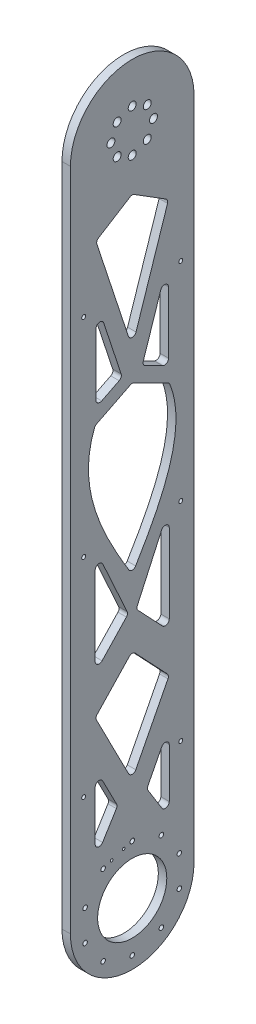
SolidWorks part; units mm, degrees
material "1060 Alloy"
ref_plane "Front Plane" through (0, 0, 0) normal (0, 0, 1) x (1, 0, 0)
ref_plane "Top Plane" through (0, 0, 0) normal (0, 1, 0) x (1, 0, 0)
ref_plane "Right Plane" through (0, 0, 0) normal (1, 0, 0) x (0, 0, -1)
sketch "Sketch1" plane through (0, 0, 0) normal (1, 0, 0) x (0, -1, 0)
  line L0 (0, 0) -> (500, 0) construction
  line L1 (0, 46.5) -> (500, 46.5)
  line L2 (0, -46.5) -> (500, -46.5)
  arc A0 (0, 46.5) -> (0, -46.5) centre (0, 0) ccw
  arc A1 (500, -46.5) -> (500, 46.5) centre (500, 0) ccw
  circle A2 centre (0, 0) radius 16 construction
  circle A3 centre (-16, 0) radius 3
  circle A4 centre (-11.3137, 11.3137) radius 3
  circle A5 centre (0, 16) radius 3
  circle A6 centre (11.3137, 11.3137) radius 3
  circle A7 centre (16, 0) radius 3
  circle A8 centre (11.3137, -11.3137) radius 3
  circle A27 centre (500, 0) radius 37.25 construction
  circle A28 centre (537.25, 0) radius 1.7
  circle A29 centre (500, 0) radius 37.25 construction
  circle A30 centre (537.25, 0) radius 1.7
  circle A31 centre (530.1359, -21.895) radius 1.7
  circle A32 centre (511.5109, -35.4269) radius 1.7
  circle A33 centre (488.4891, -35.4269) radius 1.7
  circle A34 centre (469.8641, -21.895) radius 1.7
  circle A35 centre (462.75, 0) radius 1.7
  circle A36 centre (469.8641, 21.895) radius 1.7
  circle A37 centre (488.4891, 35.4269) radius 1.7
  circle A38 centre (511.5109, 35.4269) radius 1.7
  circle A39 centre (530.1359, 21.895) radius 1.7
  circle A40 centre (500, 0) radius 26
  circle A41 centre (0, -16) radius 3
  circle A42 centre (-11.3137, -11.3137) radius 3
  point P3 (250, 0)
  point P25 (0, 0)
  point P52 (500, 0)
  point P61 (500, 0)
  dimension "D3" = 32
  dimension "D4" = 6
  dimension "D2" = 74.5
  dimension "D7" = 3.4
  dimension "D8" = 3.4
  dimension "D10" = 52
  dimension "D6" = 46.5
  dimension "D1" = 500
  dimension "D5" = 8
  dimension "D9" = 10
extrude "Boss-Extrude1" add sketch "Sketch1" along normal blind 6.35 contours L2 A1 L1 A0 A40 A39 A38 A37 A36 A35 A34 A33 A32 A31 A28 A8 A7 A6 A5 A4 A3 region at (0, -240.225, 0)
ref_axis "Axis1" through (6.35, -500, 0) along (-1, 0, 0)
sketch "Sketch3" plane through (6.35, 0, 0) normal (1, 0, 0) x (0, 0, -1)
  line L0 (0, -500) -> (0, 0) construction
  line L1 (0, -422.848) -> (27.8582, -368.6328)
  line L2 (0, -422.848) -> (-27.8582, -368.6328)
  line L3 (-27.8582, -368.6328) -> (0, -339.1393)
  line L4 (0, -339.1393) -> (27.8582, -368.6328)
  line L5 (0, -41.3687) -> (-27.3129, -58.4352)
  line L6 (-27.3129, -58.4352) -> (0, -141.249)
  line L7 (0, -141.249) -> (27.3129, -58.4352)
  line L8 (27.3129, -58.4352) -> (0, -41.3687)
  line L9 (3, -313.1891) -> (27.8582, -339.5065)
  line L10 (27.8582, -339.5065) -> (27.8582, -258.646)
  line L11 (27.8582, -258.646) -> (3, -313.1891)
  line L12 (-27.8582, -339.5065) -> (-27.8582, -258.646)
  line L13 (-3, -313.1891) -> (-27.8582, -339.5065)
  line L14 (-27.8582, -258.646) -> (-3, -313.1891)
  line L15 (-27.8582, -401.4529) -> (-11, -434.2608)
  line L16 (-11, -434.2608) -> (-27.8582, -461.4818)
  line L17 (-27.8582, -461.4818) -> (-27.8582, -401.4529)
  line L18 (11, -434.2608) -> (27.8582, -461.4818)
  line L19 (27.8582, -401.4529) -> (11, -434.2608)
  line L20 (27.8582, -461.4818) -> (27.8582, -401.4529)
  line L21 (0, -164.2489) -> (-27.8582, -178.2005)
  line L22 (0, -164.2489) -> (27.8582, -178.2005)
  line L23 (7.5, -156.821) -> (27.3129, -96.7475)
  line L24 (27.3129, -96.7475) -> (27.3129, -166.7434)
  line L25 (27.3129, -166.7434) -> (7.5, -156.821)
  line L26 (-27.3129, -96.7475) -> (-27.3129, -166.7434)
  line L27 (-7.5, -156.821) -> (-27.3129, -96.7475)
  line L28 (-27.3129, -166.7434) -> (-7.5, -156.821)
  spline S0 degree 3 poles (-27.8582, -178.2005) (-43.7791, -216.0933) (-18.6166, -258.2761) (0, -289.085) knots 0 0 0 0 1 1 1 1
  spline S1 degree 3 poles (27.8582, -178.2005) (43.7791, -216.0933) (18.6166, -258.2761) (0, -289.085) knots 0 0 0 0 1 1 1 1
  dimension "D1" = 15
  dimension "D2" = 20
  dimension "D3" = 12
  dimension "D4" = 10
  dimension "D5" = 6
  dimension "D6" = 15
  dimension "D7" = 22
extrude "Cut-Extrude1" cut sketch "Sketch3" against normal through all
fillet "Fillet1" radius 3 30 edges at (3.175, -58.4352, -27.3129) (3.175, -41.3687, 0) (3.175, -58.4352, 27.3129) (3.175, -141.249, 0) (3.175, -289.085, 0) (3.175, -164.2489, 0) (3.175, -401.4529, 27.8582) (3.175, -434.2608, 11) (3.175, -461.4818, 27.8582) (3.175, -461.4818, -27.8582) (3.175, -434.2608, -11) (3.175, -401.4529, -27.8582) (3.175, -368.6328, -27.8582) (3.175, -339.1393, 0) (3.175, -368.6328, 27.8582) (3.175, -422.848, 0) (3.175, -313.1891, 3) (3.175, -339.5065, 27.8582) (3.175, -258.646, 27.8582) (3.175, -178.2005, -27.8582) (3.175, -178.2005, 27.8582) (3.175, -339.5065, -27.8582) (3.175, -313.1891, -3) (3.175, -258.646, -27.8582) (3.175, -96.7475, 27.3129) (3.175, -166.7434, 27.3129) (3.175, -156.821, 7.5) (3.175, -166.7434, -27.3129) (3.175, -156.821, -7.5) (3.175, -96.7475, -27.3129)
sketch "Sketch4" plane through (6.35, 0, 0) normal (1, 0, 0) x (0, 0, -1)
  line L0 (0, 46.5) -> (-113.1579, 46.5) construction
  line L1 (-46.5, 0) -> (-46.5, -500) construction
  line L2 (-46.5, -100) -> (46.5, -100) construction
  line L3 (46.5, 0) -> (46.5, -500) construction
  line L4 (-46.5, -106.35) -> (46.5, -106.35) construction
  line L5 (-36.5, -100) -> (-36.5, -106.35) construction
  line L6 (0, 0) -> (0, -106.35) construction
  line L7 (0, -106.35) -> (0, -256.35) construction
  line L8 (0, -256.35) -> (46.5, -256.35) construction
  line L9 (46.5, -262.7) -> (-46.5, -262.7) construction
  line L10 (0, -181.35) -> (46.5, -181.35) construction
  line L11 (0, -262.7) -> (0, -412.7) construction
  line L12 (0, -412.7) -> (46.5, -412.7) construction
  line L13 (0, -337.7) -> (46.5, -337.7) construction
  arc A1 (46.5, 0) -> (-46.5, 0) centre (0, 0) ccw construction
  circle A2 centre (-36.5, -103.175) radius 1.5
  circle A3 centre (36.5, -103.175) radius 1.5
  circle A4 centre (-36.5, -259.525) radius 1.5
  circle A5 centre (36.5, -259.525) radius 1.5
  circle A6 centre (-36.5, -415.875) radius 1.5
  circle A7 centre (36.5, -415.875) radius 1.5
  point P17 (-36.5, -103.175)
  dimension "D1" = 3
  dimension "D2" = 6.35
  dimension "D3" = 10
  dimension "D4" = 146.5
  dimension "D5" = 150
  dimension "D6" = 6.35
  dimension "D7" = 81.35
  dimension "D8" = 150
  dimension "D9" = 81.35
extrude "Cut-Extrude2" cut sketch "Sketch4" against normal through all
sketch "Sketch5" plane through (6.35, 0, 0) normal (1, 0, 0) x (0, 0, -1)
  line L0 (-6.4835, -464.6746) -> (-15.5185, -467.6102) construction
  line L1 (-7.2252, -475.0096) -> (7.4545, -470.2399) construction
  line L2 (-21.895, -469.8641) -> (0, -462.75) construction
  line L3 (-10.9475, -466.3071) -> (0, -500) construction
  circle A0 centre (-6.4835, -464.6746) radius 1
  circle A1 centre (-15.5185, -467.6102) radius 1
  circle A2 centre (0, -500) radius 26 construction
  circle A3 centre (0, -500) radius 26 construction
  circle A4 centre (0, -462.75) radius 1.7 construction
  circle A5 centre (-21.895, -469.8641) radius 1.7 construction
  circle A6 centre (0, -462.75) radius 1.7 construction
  circle A7 centre (-21.895, -469.8641) radius 1.7 construction
  point P16 (-11.001, -466.1424)
  dimension "D1" = 2
  dimension "D2" = 9.5
  dimension "D3" = 9.6
extrude "Cut-Extrude4" cut sketch "Sketch5" against normal through all
equation "\"L1L\"=500"
equation "\"D1@Sketch1\"=\"L1L\""
equation "\"L1Thick\"=6.35"
equation "\"D1@Boss-Extrude1\"=\"L1Thick\""
equation "\"Harm-Drive-Outer\"=74.5"
equation "\"D2@Sketch1\"=\"Harm-Drive-Outer\""
